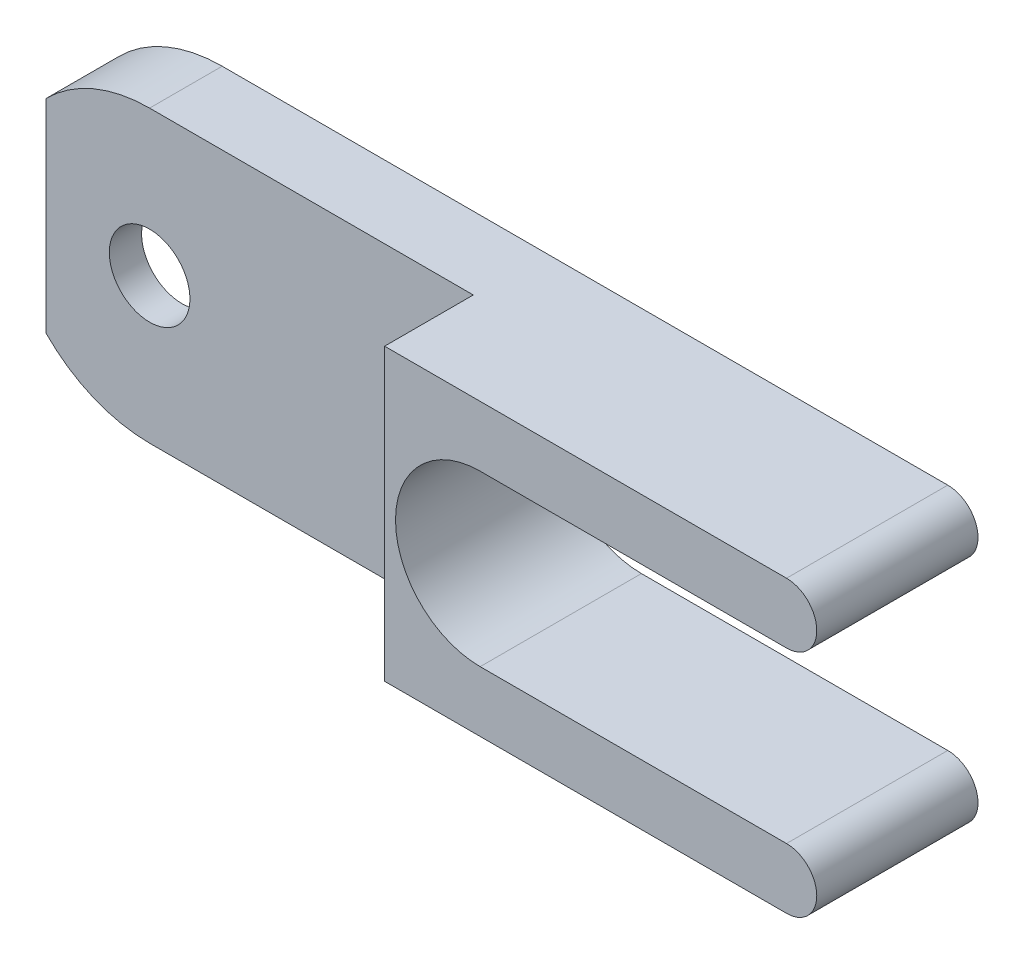
SolidWorks part; units mm, degrees
ref_plane "Front Plane" through (0, 0, 0) normal (0, 0, 1) x (1, 0, 0)
ref_plane "Top Plane" through (0, 0, 0) normal (0, 1, 0) x (1, 0, 0)
ref_plane "Right Plane" through (0, 0, 0) normal (1, 0, 0) x (0, 0, -1)
sketch "Esquisse1" plane through (0, 0, 0) normal (0, 0, 1) x (1, 0, 0)
  line L0 (-4.3758, 4.25) -> (-6.4265, 6.3008)
  line L1 (4.3758, 4.25) -> (17.3156, 2.7822)
  line L2 (17.3156, -2.7822) -> (4.3758, -4.25)
  line L3 (26, 5.25) -> (45, 5.25)
  line L4 (0, 9) -> (45, 9)
  line L5 (0, -9) -> (45, -9)
  line L6 (-4.3758, -4.25) -> (-6.4265, -6.3008)
  line L7 (26, -5.25) -> (45, -5.25)
  arc A0 (4.3758, 4.25) -> (-4.3758, 4.25) centre (0, 0) ccw
  arc A1 (17.3156, -2.7822) -> (17.3156, 2.7822) centre (17, 0) ccw
  arc A2 (4.3758, -4.25) -> (-4.3758, -4.25) centre (0, 0) cw
  arc A3 (-6.4265, 6.3008) -> (0, 9) centre (0, 0) cw
  arc A4 (45, -5.25) -> (45, -9) centre (45, -7.125) cw
  arc A5 (-6.4265, -6.3008) -> (0, -9) centre (0, 0) ccw
  arc A6 (45, 9) -> (45, 5.25) centre (45, 7.125) cw
  arc A7 (26, 5.25) -> (26, -5.25) centre (26, 0) ccw
  point P18 (34.6732, -9)
  point P21 (33.8643, -5.25)
  point P23 (28.0321, 5.25)
  point P24 (39.654, 7.125)
  point P25 (35.9078, 5.25)
  point P26 (0, 0)
  dimension "D2" = 6.1
  dimension "D3" = 2.8
  dimension "D5" = 5.25
  dimension "D6" = 9
  dimension "D8" = 45
  dimension "D1" = 8.5
  dimension "D4" = 17
  dimension "D7" = 26
extrude "Main" add sketch "Esquisse1" along normal blind 10
sketch "Sketch1" plane through (0, 0, 10) normal (0, 0, 1) x (1, 0, 0)
  line L0 (45, 9) -> (0, 9) construction
  line L1 (20.0735, 9) -> (-6.4265, 9)
  line L2 (20.0735, 9) -> (20.0735, -9)
  line L3 (20.0735, -9) -> (-6.4265, -9)
  line L4 (-6.4265, 9) -> (-6.4265, -9)
  line L6 (0, -9) -> (45, -9) construction
  point P8 (24.3648, -9)
  dimension "D1" = 26.5
extrude "Cut-Extrude1" cut sketch "Sketch1" against normal blind 7.5
sketch "Esquisse2" plane through (0, 0, 2.5) normal (0, 0, -1) x (-1, 0, 0)
  line L0 (0, -9) -> (-20.0735, -9)
  line L1 (0, -9) -> (-45, -9) construction
  line L2 (4.3758, 4.25) -> (6.4265, 6.3008) construction
  line L3 (0, 9) -> (-20.0735, 9)
  line L4 (6.4265, -6.3008) -> (6.4265, 6.3008)
  line L5 (-45, 9) -> (-20.0735, 9) construction
  line L6 (-45, 9) -> (-20.0735, 9) construction
  line L7 (-20.0735, -9) -> (-45, -9) construction
  line L8 (-20.0735, -9) -> (-20.0735, 9) construction
  line L9 (-20.0735, 9) -> (-20.0735, -9)
  arc A1 (0, -9) -> (6.4265, -6.3008) centre (0, 0) ccw
  circle A2 centre (0, 0) radius 2.5
  arc A3 (6.4265, 6.3008) -> (0, 9) centre (0, 0) ccw
  arc A6 (0, -9) -> (6.4265, -6.3008) centre (0, 0) ccw construction
  dimension "D1" = 5
extrude "Boss-Extrude1" add sketch "Esquisse2" against normal blind 2
